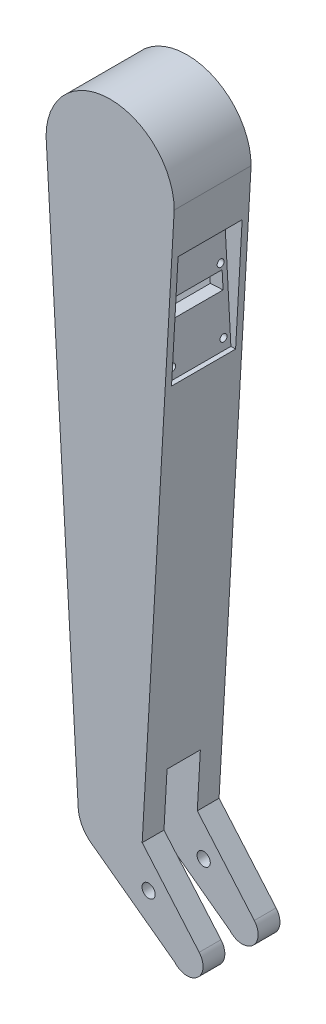
SolidWorks part; units mm, degrees
ref_plane "Plan de face" through (0, 0, 0) normal (0, 0, 1) x (1, 0, 0)
ref_plane "Plan de dessus" through (0, 0, 0) normal (0, 1, 0) x (1, 0, 0)
ref_plane "Plan de droite" through (0, 0, 0) normal (1, 0, 0) x (0, 0, -1)
sketch "Esquisse1" plane through (0, 0, 0) normal (0, 0, 1) x (1, 0, 0)
  line L0 (0, -110) -> (0, 110) construction
  line L1 (-25, 110) -> (-12.5, -110)
  line L2 (0, -110) -> (30, -140) construction
  line L3 (25, 110) -> (12.5, -110)
  line L4 (12.5, -110) -> (34.7438, -135.9307)
  line L5 (34.7438, -135.9307) -> (48.7, -152.2003) construction
  line L6 (34.7438, -135.9307) -> (25.2562, -144.0693) construction
  line L7 (25.2562, -144.0693) -> (-7.4015, -120.0731)
  line L8 (-7.4015, -120.0731) -> (-23.8801, -107.9651) construction
  circle A1 centre (0, 110) radius 25
  circle A6 centre (0, -110) radius 12.5
  circle A7 centre (30, -140) radius 6.25
  circle A8 centre (15, -125) radius 2.575
  point P5 (0, 0)
  point P8 (0, -110)
  dimension "D1" = 25
  dimension "D2" = 50
  dimension "D3" = 220
  dimension "D4" = 250
  dimension "D6" = 12.5
  dimension "D8" = 5.15
  dimension "D5" = 135
  dimension "D7" = 42.4264
extrude "Boss.-Extru.1" add sketch "Esquisse1" along normal blind 30 contours A6 L3 A1 L1 | A6 | A7 L4 A6 L7 | A7 | L3 A1 L1 region at (0, 110.0001, 0) region at (0, 4.1251, 0) region at (0, -110, 0) region at (23.2106, -123.3182, 0) region at (30, -140, 0)
sketch "Esquisse2" plane through (0, 0, 0) normal (1, 0, 0) x (0, 0, -1)
  line L0 (0, 0) -> (-30, 0) construction
  line L1 (-30, 110) -> (-30, -110) construction
  line L2 (-15, 156.2152) -> (-15, -156.2152) construction
  line L3 (-30, -110) -> (0, -110) construction
  line L4 (-27.5, 47.5) -> (-2.5, 47.5)
  line L5 (-27.5, 47.5) -> (-27.5, 92.5)
  line L6 (-27.5, 92.5) -> (-2.5, 92.5)
  line L7 (-2.5, 47.5) -> (-2.5, 92.5)
  line L8 (-27.5, 47.5) -> (-2.5, 92.5) construction
  line L9 (-27.5, 92.5) -> (-2.5, 47.5) construction
  line L10 (-8.5, -190) -> (-21.5, -190)
  line L11 (-8.5, -190) -> (-8.5, -110)
  line L12 (-8.5, -110) -> (-21.5, -110)
  line L13 (-21.5, -190) -> (-21.5, -110)
  line L14 (-8.5, -190) -> (-21.5, -110) construction
  line L15 (-8.5, -110) -> (-21.5, -190) construction
  point P6 (-15, 70)
  point P8 (-15, 0)
  point P13 (-15, -150)
  dimension "D1" = 45
  dimension "D2" = 25
  dimension "D3" = 70
  dimension "D4" = 13
  dimension "D5" = 80
extrude "Enlèv. mat.-Extru.1" cut sketch "Esquisse2" against normal through all both and the other way through all
ref_plane "Plan1" through (17.2524, 0.9802, 0) normal (-0.9984, -0.0567, 0) x (0, 0, 1)
sketch "Esquisse3" plane through (17.2524, 0.9802, 0) normal (-0.9984, -0.0567, 0) x (0, 0, 1)
  line L0 (30, 111.241) -> (30, -109.1138) construction
  line L5 (0, 111.241) -> (30, 111.241)
  line L6 (0, 111.241) -> (0, 31.241)
  line L11 (0, 31.241) -> (30, 31.241)
  line L13 (30, 111.241) -> (30, 31.241)
  line L14 (25.9386, 72.5016) -> (4.4383, 72.5016)
  line L15 (25.9386, 72.5016) -> (25.9386, 65.8266)
  line L16 (25.9386, 65.8266) -> (4.4383, 65.8266)
  line L17 (4.4383, 72.5016) -> (4.4383, 65.8266)
  circle A6 centre (5.1383, 50.4016) radius 1.35
  circle A7 centre (25.1383, 50.4016) radius 1.35
  circle A10 centre (4.8883, 74.8516) radius 1.35
  circle A11 centre (25.3883, 74.8516) radius 1.35
  dimension "D1" = 80
  dimension "D2" = 2.7
extrude "Boss.-Extru.2" add sketch "Esquisse3" against normal blind 5 contours L5 L6 L11 A11 A10 A7 A6 region at (10.9905, 111.1891, 15)
chamfer "Chanfrein1" distance 20 angle 45 1 edges at (12.5, -110, 15) first distance on face at (0, -110, 15)
